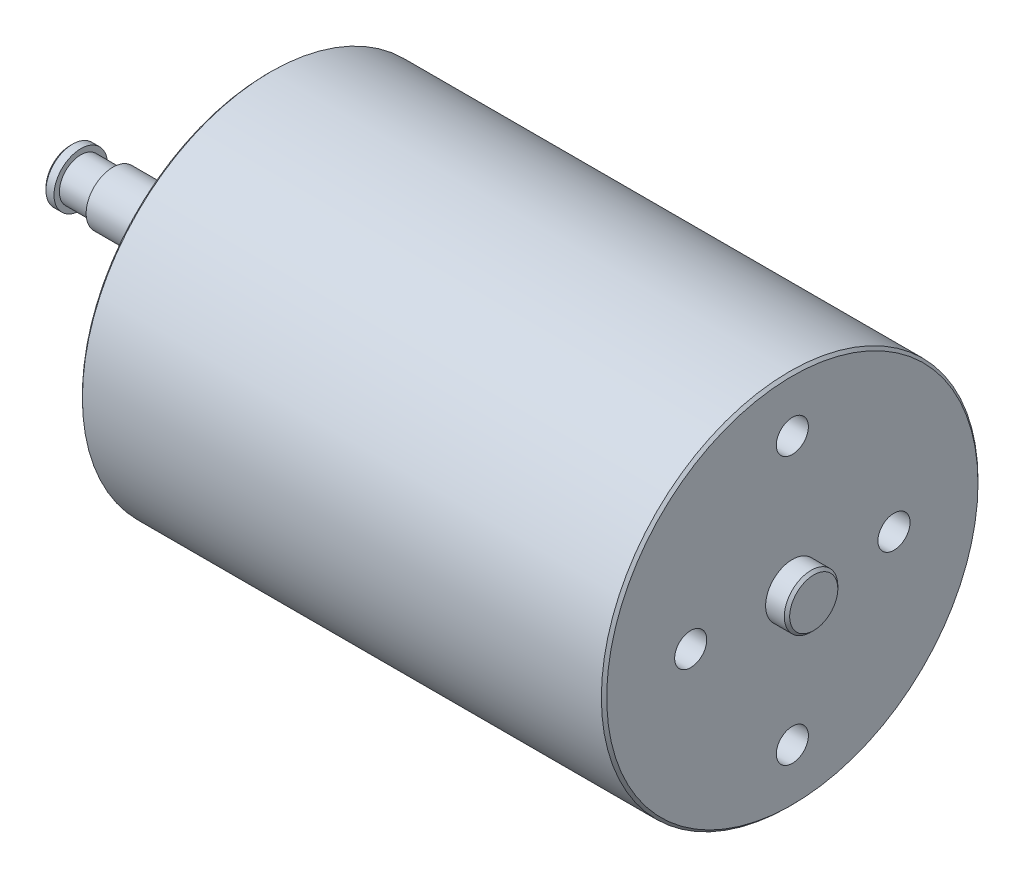
SolidWorks part; units mm, degrees
material "Custom Plastic"
ref_plane "Front Plane" through (0, 0, 0) normal (0, 0, 1) x (1, 0, 0)
ref_plane "Top Plane" through (0, 0, 0) normal (0, 1, 0) x (1, 0, 0)
ref_plane "Right Plane" through (0, 0, 0) normal (1, 0, 0) x (0, 0, -1)
sketch "Sketch1" plane through (0, 0, 0) normal (1, 0, 0) x (0, 0, -1)
  circle A0 centre (0, 0) radius 17.6
  dimension "D1" = 35.2
extrude "Boss-Extrude1" add sketch "Sketch1" along normal blind 49
sketch "Sketch2" plane through (49, 0, 0) normal (1, 0, 0) x (0, 0, -1)
  line L0 (0, 17.6) -> (0, -17.6) construction
  line L1 (-17.6, 0) -> (17.6, 0) construction
  line L2 (0, 12.5) -> (0, -12.5)
  line L3 (-9.5, 0) -> (9.5, 0)
  circle A0 centre (0, 0) radius 17.6 construction
  circle A1 centre (0, 12.5) radius 0.9042
  circle A2 centre (9.5, 0) radius 0.9941
  circle A3 centre (0, -12.5) radius 1.4367
  circle A4 centre (-9.5, 0) radius 0.8284
  dimension "D1" = 19
  dimension "D2" = 25
hole_wizard "Ø3.0 (3) Diameter Hole1" positions "Sketch3" profile "Sketch5" hole size "Ø3.0" standard "ANSI Metric"
sketch "Sketch3" plane through (49, 0, 0) normal (1, 0, 0) x (0, 0, -1)
  point P0 (0, 12.5)
  point P3 (9.5, 0)
  point P6 (0, -12.5)
  point P9 (-9.5, 0)
sketch "Sketch5" plane through (49, 12.5, 0) normal (0, 1, 0) x (0, 0, -1)
  line L0 (0, 0) -> (0, 5.9013)
  line L1 (0, 5.9013) -> (1.5, 5)
  line L2 (1.5, 5) -> (1.5, 0)
  line L5 (1.5, 0) -> (0, 0)
  line L10 (0, 5.9013) -> (-1.5, 5) construction
  line L11 (0, -6.35) -> (0, 107.95) construction
  dimension "Hole Dia." = 3
  dimension "Hole Depth" = 5
  dimension "Drill Angle" = 118
sketch "Sketch6" plane through (49, 0, 0) normal (1, 0, 0) x (0, 0, -1)
  circle A0 centre (0, 0) radius 2.5
  dimension "D1" = 5
extrude "Boss-Extrude2" add sketch "Sketch6" along normal blind 2
sketch "Sketch7" plane through (0, 0, 0) normal (-1, 0, 0) x (0, 0, 1)
  circle A0 centre (0, 0) radius 2.5
  dimension "D1" = 5
extrude "Boss-Extrude3" add sketch "Sketch7" along normal blind 14.5
sketch "Sketch8" plane through (-14.5, 0, 0) normal (-1, 0, 0) x (0, 0, 1)
  circle A0 centre (0, 0) radius 2
  dimension "D1" = 4
extrude "Boss-Extrude4" add sketch "Sketch8" along normal blind 3
extrude "Boss-Extrude5" add sketch "Sketch7<2>" along normal blind 1 from offset 17.5
sketch "Sketch7<2>" plane through (0, 0, 0) normal (-1, 0, 0) x (0, 0, 1) same geometry as "Sketch7"
chamfer "Chamfer1" distance 0.25 angle 45 4 edges at (51, 0, -2.5) (-18.5, 0, 2.5) (0, 0, -17.6) (49, 0, -17.6)
sketch "Sketch9" plane through (0, 0, 0) normal (0, 0, 1) x (1, 0, 0)
  line L0 (-14.5, -2.5) -> (0, -2.5) construction
  line L1 (-10, -2.5) -> (-2, -2.5)
  line L2 (-10, -2.5) -> (-10, -2)
  line L3 (-10, -2) -> (-2, -2)
  line L4 (-2, -2.5) -> (-2, -2)
  line L5 (0, 17.6) -> (0, -17.6) construction
  dimension "D1" = 2
  dimension "D2" = 8
  dimension "D3" = 0.5
extrude "Cut-Extrude1" cut sketch "Sketch9" against normal through all and the other way through all
